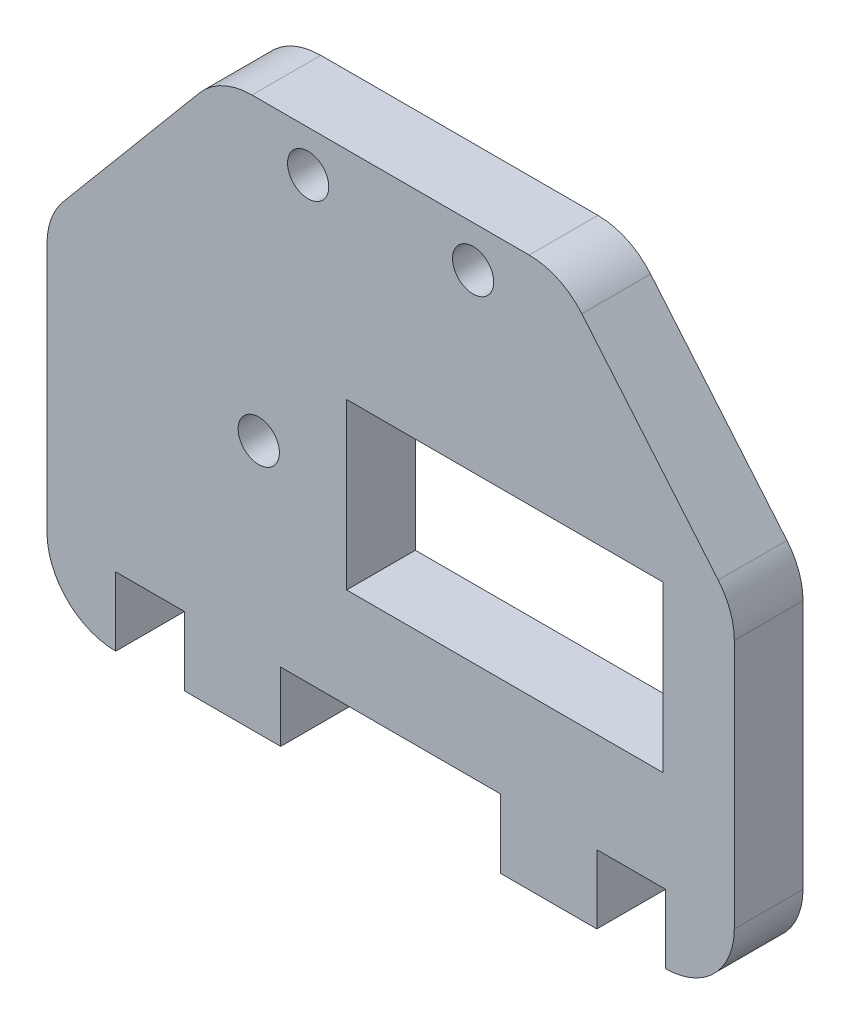
SolidWorks part; units mm, degrees
material "Acrylic (Medium-high impact)"
ref_plane "Front Plane" through (0, 0, 0) normal (0, 0, 1) x (1, 0, 0)
ref_plane "Top Plane" through (0, 0, 0) normal (0, 1, 0) x (1, 0, 0)
ref_plane "Right Plane" through (0, 0, 0) normal (1, 0, 0) x (0, 0, -1)
sketch "Sketch1" plane through (0, 0, 0) normal (0, 0, 1) x (1, 0, 0)
  line L0 (28.2311, 10.1874) -> (15.6446, 25.1874)
  line L1 (-9.1824, 25.1874) -> (15.6446, 25.1874)
  line L2 (-21.7689, 10.1874) -> (-21.7689, -14.8126)
  line L3 (-21.7689, -14.8126) -> (-16.7689, -14.8126)
  line L4 (28.2311, 10.1874) -> (28.2311, -14.8126)
  line L5 (3.2311, 25.1874) -> (3.2311, -9.8126) construction
  line L6 (-21.7689, 10.1874) -> (-9.1824, 25.1874)
  line L7 (23.2311, -14.8126) -> (28.2311, -14.8126)
  line L8 (0.0311, 9.4459) -> (23.0311, 9.4459)
  line L9 (0.0311, 9.4459) -> (0.0311, -2.5541)
  line L10 (0.0311, -2.5541) -> (23.0311, -2.5541)
  line L11 (23.0311, 9.4459) -> (23.0311, -2.5541)
  line L13 (-16.7689, -14.8126) -> (-16.7689, -9.8126)
  line L14 (-16.7689, -9.8126) -> (-11.7689, -9.8126)
  line L15 (23.2311, -14.8126) -> (23.2311, -9.8126)
  line L16 (-11.7689, -14.8126) -> (-11.7689, -9.8126)
  line L17 (-11.7689, -9.8126) -> (-11.7689, -14.8126) construction
  line L18 (-11.7689, -14.8126) -> (-4.7689, -14.8126)
  line L19 (-4.7689, -9.8126) -> (-4.7689, -14.8126) construction
  line L20 (-4.7689, -14.8126) -> (-4.7689, -9.8126)
  line L21 (18.2311, -14.8126) -> (18.2311, -9.8126)
  line L22 (18.2311, -9.8126) -> (18.2311, -14.8126) construction
  line L23 (18.2311, -14.8126) -> (11.2311, -14.8126)
  line L24 (11.2311, -9.8126) -> (11.2311, -14.8126) construction
  line L25 (11.2311, -14.8126) -> (11.2311, -9.8126)
  line L26 (-4.7689, -9.8126) -> (11.2311, -9.8126)
  line L27 (18.2311, -9.8126) -> (23.2311, -9.8126)
  circle A1 centre (-2.7689, 22.1874) radius 1.5
  circle A3 centre (9.2311, 22.1874) radius 1.5
  circle A8 centre (-6.3619, 3.6459) radius 1.5
  dimension "D11" = 3
  dimension "D12" = 3
  dimension "D1" = 50
  dimension "D2" = 12
  dimension "D3" = 25
  dimension "D4" = 40
  dimension "D5" = 40
  dimension "D6" = 23
  dimension "D7" = 5.2
  dimension "D8" = 40
  dimension "D9" = 20
  dimension "D10" = 5
  dimension "D13" = 6
  dimension "D14" = 6
  dimension "D15" = 3
  dimension "D16" = 3
extrude "Boss-Extrude1" add sketch "Sketch1" along normal blind 5
fillet "Fillet1" radius 5 1 edges at (15.6446, 25.1874, 2.5) type face fillet first side face at (3.2311, 25.1874, 2.5) second side face at (21.9378, 17.6874, 2.5)
fillet "Fillet2" radius 5 1 edges at (28.2311, 10.1874, 2.5) type face fillet first side face at (22.6872, 16.7943, 2.5) second side face at (28.2311, -2.3126, 2.5)
fillet "Fillet3" radius 5 1 edges at (28.2311, -14.8126, 2.5) type face fillet first side face at (28.2311, -3.2225, 2.5) second side face at (25.7311, -14.8126, 2.5)
fillet "Fillet4" radius 5 1 edges at (-9.1824, 25.1874, 2.5) type face fillet first side face at (2.0653, 25.1874, 2.5) second side face at (-15.4757, 17.6874, 2.5)
fillet "Fillet5" radius 5 1 edges at (-21.7689, 10.1874, 2.5) type face fillet first side face at (-16.225, 16.7943, 2.5) second side face at (-21.7689, -2.3126, 2.5)
fillet "Fillet6" radius 5 1 edges at (-21.7689, -14.8126, 2.5) type face fillet first side face at (-21.7689, -3.2225, 2.5) second side face at (-19.2689, -14.8126, 2.5)
